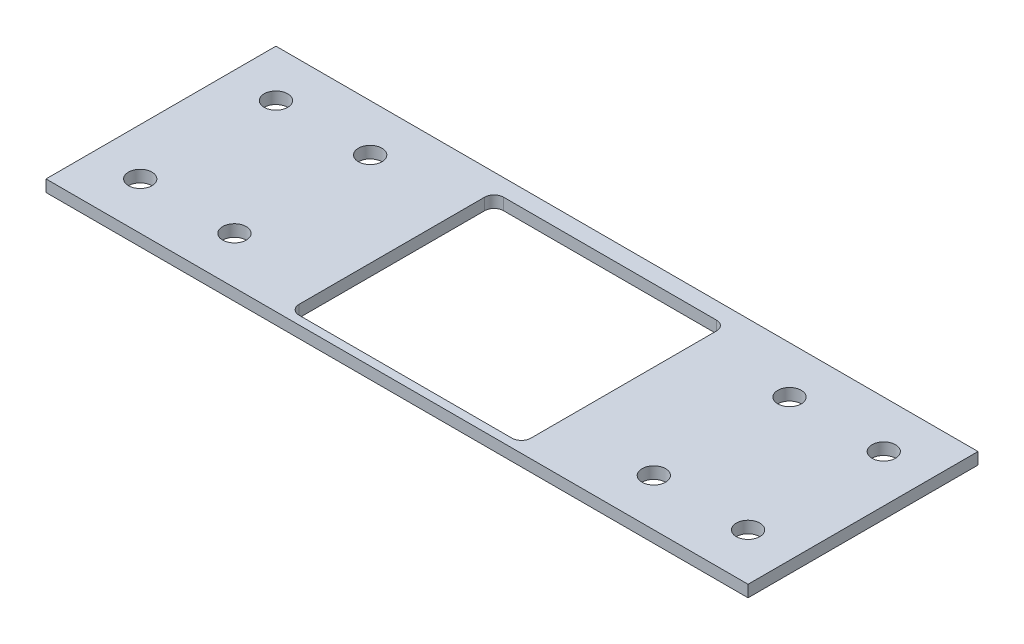
SolidWorks part; units mm, degrees
ref_plane "Front Plane" through (0, 0, 0) normal (0, 0, 1) x (1, 0, 0)
ref_plane "Top Plane" through (0, 0, 0) normal (0, 1, 0) x (1, 0, 0)
ref_plane "Right Plane" through (0, 0, 0) normal (1, 0, 0) x (0, 0, -1)
sketch "Sketch1" plane through (0, 0, 0) normal (0, 1, 0) x (1, 0, 0)
  line L1 (69.215, -30.988) -> (-69.215, -30.988)
  line L2 (69.215, -30.988) -> (69.215, 30.988)
  line L3 (69.215, 30.988) -> (-69.215, 30.988)
  line L4 (-69.215, -30.988) -> (-69.215, 30.988)
  line L5 (69.215, -30.988) -> (-69.215, 30.988) construction
  line L6 (69.215, 30.988) -> (-69.215, -30.988) construction
  point P0 (0, 0)
  dimension "D1" = 61.976
  dimension "D2" = 138.43
extrude "Boss-Extrude1" add sketch "Sketch1" along normal blind 25.4
sketch "Sketch2" plane through (-69.215, 0, 0) normal (-1, 0, 0) x (0, 0, 1)
  line L0 (-30.988, 25.4) -> (-30.988, 0) construction
  line L1 (30.988, 22.225) -> (-30.988, 22.225)
  line L2 (30.988, 22.225) -> (30.988, 0)
  line L3 (30.988, 0) -> (-30.988, 0)
  line L4 (-30.988, 22.225) -> (-30.988, 0)
  line L5 (30.988, 22.225) -> (-30.988, 0) construction
  line L6 (30.988, 0) -> (-30.988, 22.225) construction
  line L7 (30.988, 25.4) -> (30.988, 0) construction
  line L8 (-30.988, 25.4) -> (30.988, 25.4) construction
  line L9 (-30.988, 0) -> (30.988, 0) construction
  point P0 (0, 11.1125)
  dimension "D1" = 0
  dimension "D2" = 0
  dimension "D3" = 3.175
  dimension "D4" = 0
extrude "Cut-Extrude1" cut sketch "Sketch2" against normal up to next
sketch "Sketch3" plane through (0, 25.4, 0) normal (0, 1, 0) x (1, 0, 0)
  line L1 (69.215, 30.988) -> (-69.215, 30.988) construction
  line L2 (-69.215, -30.988) -> (69.215, -30.988) construction
  line L3 (-69.215, 30.988) -> (-69.215, -30.988) construction
  line L4 (-69.215, 0) -> (69.215, 0) construction
  line L5 (69.215, -30.988) -> (69.215, 30.988) construction
  line L6 (0, 30.988) -> (0, -30.988) construction
  circle A0 centre (-56.515, 18.288) radius 3.175
  circle A1 centre (-56.515, -18.288) radius 3.175
  circle A5 centre (56.515, -18.288) radius 3.175
  circle A6 centre (56.515, 18.288) radius 3.175
  dimension "D2" = 6.35
  dimension "D3" = 12.7
  dimension "D4" = 12.7
extrude "Cut-Extrude2" cut sketch "Sketch3" against normal through all
sketch "Sketch5" plane through (-69.215, 0, 0) normal (-1, 0, 0) x (0, 0, 1)
  line L4 (-30.988, 25.4) -> (-30.988, 22.225)
  line L5 (-30.988, 22.225) -> (30.988, 22.225)
  line L6 (30.988, 22.225) -> (30.988, 25.4)
  line L7 (30.988, 25.4) -> (-30.988, 25.4)
  line L8 (-30.988, 25.4) -> (-30.988, 22.225)
  line L9 (-30.988, 22.225) -> (30.988, 22.225)
  line L10 (30.988, 22.225) -> (30.988, 25.4)
  line L11 (30.988, 25.4) -> (-30.988, 25.4)
  dimension "D1" = 0
extrude "Boss-Extrude2" add sketch "Sketch5" along normal blind 25.4
sketch "Sketch7" plane through (69.215, 0, 0) normal (1, 0, 0) x (0, 0, -1)
  line L4 (-30.988, 25.4) -> (-30.988, 22.225)
  line L5 (-30.988, 22.225) -> (30.988, 22.225)
  line L6 (30.988, 22.225) -> (30.988, 25.4)
  line L7 (30.988, 25.4) -> (-30.988, 25.4)
  line L8 (-30.988, 25.4) -> (-30.988, 22.225)
  line L9 (-30.988, 22.225) -> (30.988, 22.225)
  line L10 (30.988, 22.225) -> (30.988, 25.4)
  line L11 (30.988, 25.4) -> (-30.988, 25.4)
  dimension "D1" = 0
extrude "Boss-Extrude3" add sketch "Sketch7" along normal blind 25.4
sketch "Sketch8" plane through (0, 25.4, 0) normal (0, 1, 0) x (1, 0, 0)
  line L0 (-69.215, -30.988) -> (-69.215, 30.988) construction
  line L1 (-94.615, -30.988) -> (94.615, -30.988) construction
  line L2 (94.615, 30.988) -> (-94.615, 30.988) construction
  line L3 (69.215, 30.988) -> (69.215, -30.988) construction
  line L4 (-94.615, -30.988) -> (-94.615, 30.988) construction
  line L5 (94.615, 30.988) -> (94.615, -30.988) construction
  line L6 (-94.615, 0) -> (94.615, 0) construction
  line L7 (0, 30.988) -> (0, -30.988) construction
  circle A0 centre (-81.915, 18.288) radius 3.175
  circle A1 centre (-81.915, -18.288) radius 3.175
  circle A2 centre (81.915, -18.288) radius 3.175
  circle A3 centre (81.915, 18.288) radius 3.175
  dimension "D3" = 6.35
  dimension "D4" = 12.7
  dimension "D5" = 12.7
  dimension "D1" = 25.4
  dimension "D2" = 25.4
extrude "Cut-Extrude3" cut sketch "Sketch8" against normal up to next
sketch "Sketch9" plane through (0, 25.4, 0) normal (0, 1, 0) x (1, 0, 0)
  line L0 (94.615, 30.988) -> (-94.615, 30.988) construction
  line L1 (40.64, -28.702) -> (-40.64, -28.702)
  line L2 (40.64, -28.702) -> (40.64, 26.416)
  line L3 (40.64, 26.416) -> (-40.64, 26.416)
  line L4 (-40.64, -28.702) -> (-40.64, 26.416)
  line L5 (40.64, -28.702) -> (-40.64, 26.416) construction
  line L6 (40.64, 26.416) -> (-40.64, -28.702) construction
  line L7 (-40.64, -28.702) -> (-31.242, -28.702)
  line L8 (-40.64, -28.702) -> (-40.64, 26.416)
  line L9 (-40.64, 26.416) -> (-31.242, 26.416)
  line L10 (-31.242, -28.702) -> (-31.242, 26.416)
  line L11 (40.64, 26.416) -> (31.242, 26.416)
  line L12 (40.64, 26.416) -> (40.64, -28.702)
  line L13 (40.64, -28.702) -> (31.242, -28.702)
  line L14 (31.242, 26.416) -> (31.242, -28.702)
  line L16 (0, 26.416) -> (0, -28.702) construction
  line L17 (-94.615, -30.988) -> (94.615, -30.988) construction
  point P0 (0, -1.143)
  point P5 (0, 0)
  point P10 (0, 0)
  dimension "D1" = 2.286
  dimension "D2" = 81.28
  dimension "D3" = 9.398
  dimension "D4" = 9.398
  dimension "D5" = 4.572
extrude "Cut-Extrude4" cut sketch "Sketch9" against normal through all contours L14 L3 L10 L1 region at (0, 25.4, 1.143)
fillet "Fillet1" radius 2.54 4 edges at (31.242, 23.8125, 28.702) (-31.242, 23.8125, 28.702) (31.242, 23.8125, -26.416) (-31.242, 23.8125, -26.416)
